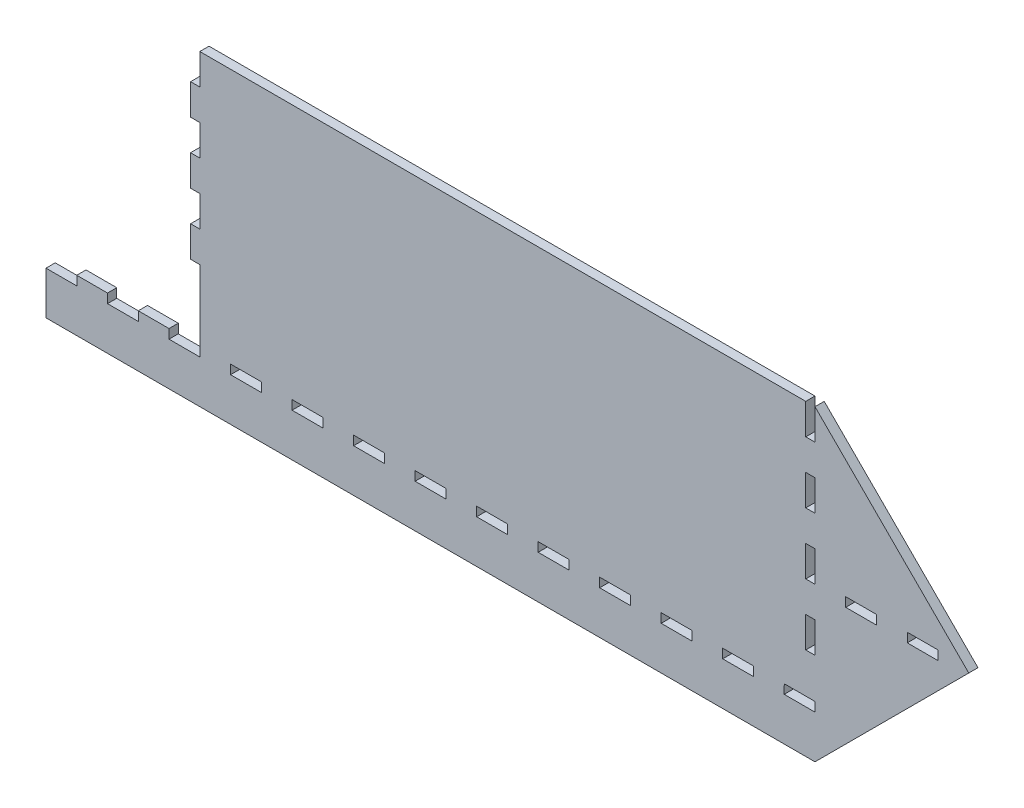
SolidWorks part; units mm, degrees
ref_plane "Front Plane" through (0, 0, 0) normal (0, 0, 1) x (1, 0, 0)
ref_plane "Top Plane" through (0, 0, 0) normal (0, 1, 0) x (1, 0, 0)
ref_plane "Right Plane" through (0, 0, 0) normal (1, 0, 0) x (0, 0, -1)
sketch "Sketch1" plane through (0, 0, 0) normal (0, 0, 1) x (1, 0, 0)
  line L0 (-112.631, -67.7284) -> (-112.631, -53.7284)
  line L1 (-62.631, 22.2716) -> (-65.631, 22.2716)
  line L2 (-102.631, -50.7284) -> (-92.631, -50.7284)
  line L3 (-62.631, 32.2716) -> (137.369, 32.2716)
  line L4 (137.369, 32.2716) -> (187.369, -17.7284)
  line L5 (187.369, -17.7284) -> (137.369, -67.7284)
  line L6 (137.369, -67.7284) -> (-112.631, -67.7284)
  line L7 (-65.631, 22.2716) -> (-65.631, 12.2716)
  line L8 (-62.631, -50.7284) -> (-62.631, -27.7284)
  line L9 (137.369, 32.2716) -> (137.369, -67.7284) construction
  line L10 (137.369, -17.7284) -> (187.369, -17.7284) construction
  line L11 (157.369, -16.2284) -> (147.369, -16.2284)
  line L12 (177.369, -16.2284) -> (167.369, -16.2284)
  line L13 (177.369, -16.2284) -> (177.369, -19.2284)
  line L14 (177.369, -19.2284) -> (167.369, -19.2284)
  line L15 (167.369, -16.2284) -> (167.369, -19.2284)
  line L16 (177.369, -16.2284) -> (167.369, -19.2284) construction
  line L17 (177.369, -19.2284) -> (167.369, -16.2284) construction
  line L18 (157.369, -16.2284) -> (157.369, -19.2284)
  line L19 (157.369, -19.2284) -> (147.369, -19.2284)
  line L20 (147.369, -16.2284) -> (147.369, -19.2284)
  line L21 (137.3812, -50.7284) -> (127.3812, -50.7284)
  line L22 (137.3812, -50.7284) -> (137.3692, -53.7284)
  line L23 (137.3692, -53.7284) -> (127.3692, -53.7284)
  line L24 (127.3812, -50.7284) -> (127.3692, -53.7284)
  line L25 (137.3812, -50.7284) -> (127.3692, -53.7284) construction
  line L26 (137.3692, -53.7284) -> (127.3812, -50.7284) construction
  line L27 (117.3811, -50.7284) -> (107.3787, -50.7284)
  line L28 (117.3811, -50.7284) -> (117.3691, -53.7284)
  line L29 (117.3691, -53.7284) -> (107.3691, -53.7284)
  line L30 (107.3787, -50.7284) -> (107.3691, -53.7284)
  line L31 (117.3811, -50.7284) -> (107.3691, -53.7284) construction
  line L32 (117.3691, -53.7284) -> (107.3787, -50.7284) construction
  line L33 (97.3787, -50.7284) -> (87.3763, -50.7284)
  line L34 (97.3787, -50.7284) -> (97.369, -53.7284)
  line L35 (97.369, -53.7284) -> (87.369, -53.7284)
  line L36 (87.3763, -50.7284) -> (87.369, -53.7284)
  line L37 (97.3787, -50.7284) -> (87.369, -53.7284) construction
  line L38 (97.369, -53.7284) -> (87.3763, -50.7284) construction
  line L39 (77.3763, -50.7284) -> (67.3738, -50.7284)
  line L40 (77.3763, -50.7284) -> (77.369, -53.7284)
  line L41 (77.369, -53.7284) -> (67.369, -53.7284)
  line L42 (67.3738, -50.7284) -> (67.369, -53.7284)
  line L43 (77.3763, -50.7284) -> (67.369, -53.7284) construction
  line L44 (77.369, -53.7284) -> (67.3738, -50.7284) construction
  line L45 (57.3738, -50.7284) -> (47.3714, -50.7284)
  line L46 (57.3738, -50.7284) -> (57.369, -53.7284)
  line L47 (57.369, -53.7284) -> (47.369, -53.7284)
  line L48 (47.3714, -50.7284) -> (47.369, -53.7284)
  line L49 (57.3738, -50.7284) -> (47.369, -53.7284) construction
  line L50 (57.369, -53.7284) -> (47.3714, -50.7284) construction
  line L51 (37.3714, -50.7284) -> (27.369, -50.7284)
  line L52 (37.3714, -50.7284) -> (37.369, -53.7284)
  line L53 (37.369, -53.7284) -> (27.369, -53.7284)
  line L54 (27.369, -50.7284) -> (27.369, -53.7284)
  line L55 (37.3714, -50.7284) -> (27.369, -53.7284) construction
  line L56 (37.369, -53.7284) -> (27.369, -50.7284) construction
  line L57 (17.369, -50.7284) -> (7.369, -50.7284)
  line L58 (17.369, -50.7284) -> (17.369, -53.7284)
  line L59 (17.369, -53.7284) -> (7.369, -53.7284)
  line L60 (7.369, -50.7284) -> (7.369, -53.7284)
  line L61 (17.369, -50.7284) -> (7.369, -53.7284) construction
  line L62 (17.369, -53.7284) -> (7.369, -50.7284) construction
  line L63 (-2.631, -50.7284) -> (-12.631, -50.7284)
  line L64 (-2.631, -50.7284) -> (-2.631, -53.7284)
  line L65 (-2.631, -53.7284) -> (-12.631, -53.7284)
  line L66 (-12.631, -50.7284) -> (-12.631, -53.7284)
  line L67 (-2.631, -50.7284) -> (-12.631, -53.7284) construction
  line L68 (-2.631, -53.7284) -> (-12.631, -50.7284) construction
  line L69 (-22.631, -50.7284) -> (-32.631, -50.7284)
  line L70 (-22.631, -50.7284) -> (-22.631, -53.7284)
  line L71 (-22.631, -53.7284) -> (-32.631, -53.7284)
  line L72 (-32.631, -50.7284) -> (-32.631, -53.7284)
  line L73 (-22.631, -50.7284) -> (-32.631, -53.7284) construction
  line L74 (-22.631, -53.7284) -> (-32.631, -50.7284) construction
  line L75 (-42.631, -50.7284) -> (-52.631, -50.7284)
  line L76 (-42.631, -50.7284) -> (-42.631, -53.7284)
  line L77 (-42.631, -53.7284) -> (-52.631, -53.7284)
  line L78 (-52.631, -50.7284) -> (-52.631, -53.7284)
  line L79 (-42.631, -50.7284) -> (-52.631, -53.7284) construction
  line L80 (-42.631, -53.7284) -> (-52.631, -50.7284) construction
  line L81 (-82.631, -50.7284) -> (-72.631, -50.7284)
  line L82 (-62.631, -50.7284) -> (-62.631, -53.7284)
  line L83 (-62.631, -53.7284) -> (-72.631, -53.7284)
  line L84 (-72.631, -50.7284) -> (-72.631, -53.7284)
  line L85 (-62.631, -50.7284) -> (-72.631, -53.7284) construction
  line L86 (-62.631, -53.7284) -> (-72.631, -50.7284) construction
  line L87 (137.369, 12.2716) -> (134.369, 12.2716)
  line L88 (-82.631, -50.7284) -> (-82.631, -53.7284)
  line L89 (-82.631, -53.7284) -> (-92.631, -53.7284)
  line L90 (-92.631, -50.7284) -> (-92.631, -53.7284)
  line L91 (-82.631, -50.7284) -> (-92.631, -53.7284) construction
  line L92 (-82.631, -53.7284) -> (-92.631, -50.7284) construction
  line L93 (137.369, 32.2716) -> (134.369, 32.2716)
  line L94 (-102.631, -50.7284) -> (-102.631, -53.7284)
  line L95 (-102.631, -53.7284) -> (-112.631, -53.7284)
  line L96 (-65.631, 12.2716) -> (-62.631, 12.2716)
  line L97 (-102.631, -50.7284) -> (-112.631, -53.7284) construction
  line L98 (-102.631, -53.7284) -> (-112.631, -50.7284) construction
  line L99 (-62.631, -50.7284) -> (-72.631, -50.7284) [skipped]
  line L100 (-82.631, -50.7284) -> (-92.631, -50.7284) [skipped]
  line L101 (-102.631, -50.7284) -> (-112.631, -50.7284) [skipped]
  line L102 (137.369, 32.2716) -> (137.369, 22.2716)
  line L103 (137.369, 22.2716) -> (134.369, 22.2716)
  line L104 (134.369, 32.2716) -> (134.369, 22.2716)
  line L105 (137.369, 12.2716) -> (137.369, 2.2716)
  line L106 (137.369, 2.2716) -> (134.369, 2.2716)
  line L107 (134.369, 12.2716) -> (134.369, 2.2716)
  line L108 (137.369, -7.7284) -> (134.369, -7.7284)
  line L109 (137.369, -7.7284) -> (137.369, -17.7284)
  line L110 (-62.631, 2.2716) -> (-65.631, 2.2716)
  line L111 (137.369, -17.7284) -> (134.369, -17.7284)
  line L113 (-65.631, 2.2716) -> (-65.631, -7.7284)
  line L114 (157.369, -16.2284) -> (147.369, -19.2284) construction
  line L115 (-65.631, -7.7284) -> (-62.631, -7.7284)
  line L116 (-62.631, 2.2716) -> (-62.631, 12.2716)
  line L117 (-62.631, -17.7284) -> (-65.631, -17.7284)
  line L118 (-65.631, -17.7284) -> (-65.631, -27.7284)
  line L119 (-65.631, -27.7284) -> (-62.631, -27.7284)
  line L120 (-62.631, -17.7284) -> (-62.631, -7.7284)
  line L121 (134.369, -7.7284) -> (134.369, -17.7284)
  line L122 (157.369, -19.2284) -> (147.369, -16.2284) construction
  line L123 (-62.631, 22.2716) -> (-62.631, 32.2716)
  line L125 (-112.631, -52.2284) -> (-112.631, -53.3547) [skipped]
  line L128 (137.369, -27.7284) -> (134.369, -27.7284)
  line L129 (137.369, -27.7284) -> (137.369, -37.7284)
  line L130 (137.369, -37.7284) -> (134.369, -37.7284)
  line L131 (134.369, -27.7284) -> (134.369, -37.7284)
  point P5 (172.369, -17.7284)
  point P9 (151.1235, -51.5486)
  point P17 (152.369, -17.7284)
  point P19 (131.1235, -51.6165)
  point P24 (111.1235, -51.6845)
  point P29 (91.1235, -51.7525)
  point P34 (71.1235, -51.8205)
  point P39 (51.1235, -51.8885)
  point P44 (31.1235, -51.9564)
  point P49 (11.1235, -52.0244)
  point P54 (-8.8765, -52.0924)
  point P59 (-28.8765, -52.1604)
  point P64 (-48.8765, -52.2284)
  point P70 (-68.8765, -52.2284)
  point P75 (-88.8765, -52.2284)
  point P80 (-108.8765, -52.2284)
  dimension "D1" = 100
  dimension "D3" = 300
  dimension "D4" = 3
  dimension "D5" = 50
  dimension "D6" = 10
  dimension "D7" = 10
  dimension "D8" = 10
  dimension "D10" = 3
  dimension "D11" = 14
  dimension "D13" = 3
  dimension "D14" = 10
  dimension "D15" = 3
  dimension "D17" = 10
  dimension "D18" = 3
  dimension "D19" = 3
  dimension "D21" = 10
  dimension "D22" = 10
  dimension "D23" = 10
  dimension "D24" = 10
  dimension "D25" = 10
  dimension "D26" = 10
  dimension "D9" = 10
  dimension "D27" = 10
  dimension "D28" = 10
  dimension "D29" = 10
  dimension "D30" = 10
  dimension "D31" = 10
  dimension "D32" = 10
  dimension "D33" = 10
  dimension "D34" = 10
  dimension "D35" = 10
  dimension "D36" = 10
  dimension "D37" = 10
  dimension "D38" = 10
  dimension "D39" = 10
  dimension "D12" = 4
  dimension "D16" = 4
extrude "Boss-Extrude1" add sketch "Sketch1" along normal blind 3 contours L94 L95 L0 L6 L5 L4 L3 L82 L83 L84 L81 L88 L89 L90 L2 L24 L21 L22 L23 L30 L27 L28 L29 L36 L33 L34 L35 L42 L39 L40 L41 L48 L45 L46 L47 region at (44.6585, -18.7021, 0)
